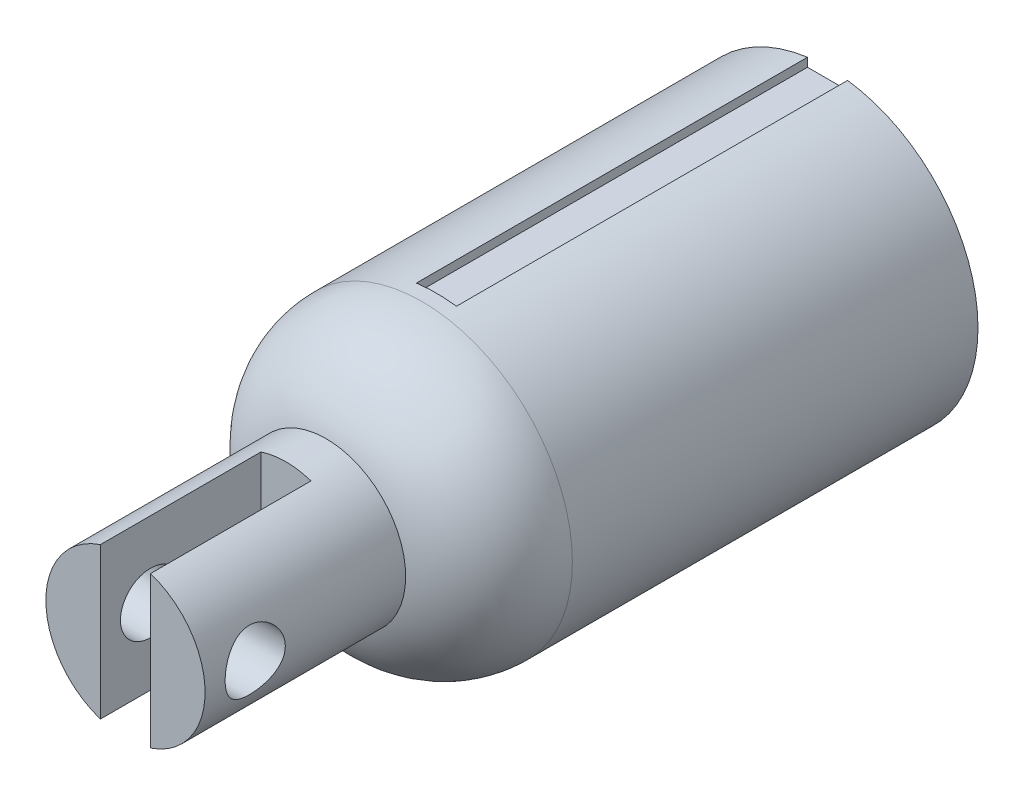
SolidWorks part; units mm, degrees
ref_plane "Alzado" through (0, 0, 0) normal (0, 0, 1) x (1, 0, 0)
ref_plane "Planta" through (0, 0, 0) normal (0, 1, 0) x (1, 0, 0)
ref_plane "Vista lateral" through (0, 0, 0) normal (1, 0, 0) x (0, 0, -1)
sketch "Croquis1" plane through (0, 0, 0) normal (0, 0, 1) x (1, 0, 0)
  circle A0 centre (0, 0) radius 7.9375
  dimension "D1" = 15.875
extrude "Saliente-Extruir1" add sketch "Croquis1" against normal blind 20
sketch "Croquis2" plane through (0, 0, -20) normal (0, 0, -1) x (-1, 0, 0)
  circle A0 centre (0, 0) radius 15
  dimension "D1" = 30
extrude "Saliente-Extruir2" add sketch "Croquis2" along normal blind 50
fillet "Redondeo1" radius 10 1 edges at (-15, 0, -20)
sketch "Croquis3" plane through (0, 0, 0) normal (0, 0, 1) x (1, 0, 0)
  line L1 (2.5, -10.5829) -> (-2.5, -10.5829)
  line L2 (2.5, -10.5829) -> (2.5, 10.5829)
  line L3 (2.5, 10.5829) -> (-2.5, 10.5829)
  line L4 (-2.5, -10.5829) -> (-2.5, 10.5829)
  line L5 (2.5, -10.5829) -> (-2.5, 10.5829) construction
  line L6 (2.5, 10.5829) -> (-2.5, -10.5829) construction
  point P0 (0, 0)
  dimension "D1" = 5
extrude "Cortar-Extruir1" cut sketch "Croquis3" against normal blind 16
sketch "Croquis4" plane through (0, 0, 0) normal (1, 0, 0) x (0, 0, -1)
  line L0 (0, 7.5335) -> (0, -7.5335) construction
  circle A0 centre (5, 0) radius 3
  dimension "D1" = 6
  dimension "D2" = 5
extrude "Cortar-Extruir2" cut sketch "Croquis4" against normal mid plane 20
sketch "Croquis5" plane through (0, 0, -70) normal (0, 0, -1) x (-1, 0, 0)
  line L0 (-15, 0) -> (15, 0) construction
  line L1 (-2, 14) -> (2, 14)
  line L2 (-2, 14) -> (-2, 16)
  line L3 (-2, 16) -> (2, 16)
  line L4 (2, 14) -> (2, 16)
  line L5 (-2, 14) -> (2, 16) construction
  line L6 (-2, 16) -> (2, 14) construction
  line L7 (-2, -16) -> (2, -14) construction
  line L8 (-2, -14) -> (2, -16) construction
  line L9 (2, -14) -> (2, -16)
  line L10 (-2, -16) -> (2, -16)
  line L11 (-2, -14) -> (-2, -16)
  line L12 (-2, -14) -> (2, -14)
  circle A0 centre (0, 0) radius 15 construction
  point P0 (0, 15)
  point P14 (0, -15)
  dimension "D1" = 2
  dimension "D2" = 4
extrude "Cortar-Extruir3" cut sketch "Croquis5" against normal blind 39
